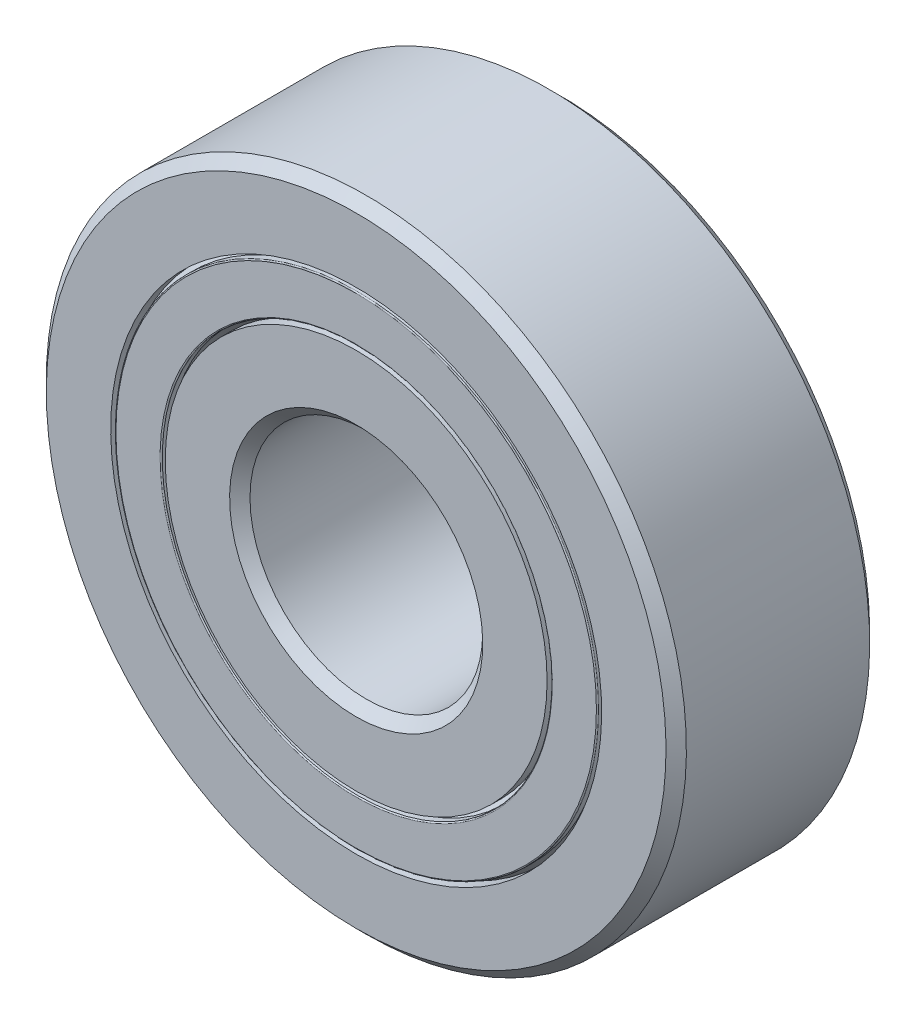
SolidWorks part; units mm, degrees
ref_plane "Front Plane" through (0, 0, 0) normal (0, 0, 1) x (1, 0, 0)
ref_plane "Top Plane" through (0, 0, 0) normal (0, 1, 0) x (1, 0, 0)
ref_plane "Right Plane" through (0, 0, 0) normal (1, 0, 0) x (0, 0, -1)
sketch "Sketch1" plane through (0, 0, 0) normal (0, 0, 1) x (1, 0, 0)
  line L0 (-11, 0) -> (11, 0) construction
  line L1 (-4, 0) -> (4, 0) construction
  circle A0 centre (0, 0) radius 4 construction
  circle A1 centre (0, 0) radius 11 construction
  point P3 (0, 0)
  point P6 (0, 0)
  point P7 (0, -4)
  point P11 (0, -11)
  point P12 (0, 4)
  point P13 (0, 11)
  dimension "OD" = 22
  dimension "ID" = 8
sketch "Sketch2" plane through (0, 0, 0) normal (1, 0, 0) x (0, 0, -1)
  line L0 (-3.5, 11) -> (3.5, 11) construction
  line L1 (0, 11) -> (0, -11) construction
  line L2 (3.15, 11) -> (-3.15, 11)
  line L3 (-3.15, 11) -> (-3.5, 10.65)
  line L4 (-3.5, 10.65) -> (-3.5, 8.4375)
  line L5 (-3.5, 8.4375) -> (-1.5556, 8.4375)
  line L6 (3.5, 8.4375) -> (1.5556, 8.4375)
  line L7 (3.5, 10.65) -> (3.5, 8.4375)
  line L8 (3.15, 11) -> (3.5, 10.65)
  line L9 (0, 11) -> (0, 7.5) construction
  line L10 (0, 7.5) -> (0, 4) construction
  line L11 (0, 11) -> (0, -11) construction
  line L12 (-3.5, 0) -> (3.5, 0) construction
  line L13 (3.5, 4) -> (-3.5, 4) construction
  line L14 (0, 9.3162) -> (0, 5.6838) construction
  line L15 (-3.5, -4) -> (3.5, -4) construction
  line L16 (-3.5, 4) -> (-3.5, -4) construction
  line L17 (3.5, 11) -> (3.5, -11) construction
  line L18 (-3.5, 8.4375) -> (-3.5, 8.3438) construction
  line L19 (-3.5, 8.3438) -> (-3.5, 8.25) construction
  line L20 (-3.5, 8.25) -> (-3.5, 8.1562) construction
  line L21 (-3.5, 8.1562) -> (-3.5, 8.0625) construction
  line L22 (-3.5, 8.0625) -> (-3.5, 7.9688) construction
  line L24 (-2.5278, 8.4375) -> (-2.5278, 7.5) construction
  arc A0 (-1.5556, 8.4375) -> (1.5556, 8.4375) centre (0, 7.5) cw
  circle A1 centre (0, 7.5) radius 1.8162 construction
  point P14 (0, 4)
  point P17 (0, 0)
  point P21 (0, 11)
  point P29 (0, 4)
  point P30 (0, -4)
  point P46 (-2.5278, 7.9688)
  dimension "Width" = 7
  dimension "D1" = 45
  dimension "D2" = 0.35
  dimension "D3" = 3.1111
  dimension "D4" = 0.9375
  dimension "For Shaft Diameter" = 8
  dimension "For Housing ID" = 22
sketch "Sketch3" plane through (0, 0, 0) normal (1, 0, 0) x (0, 0, -1)
  line L0 (3.15, 11) -> (3.5, 10.65) construction
  line L1 (3.5, 10.65) -> (3.5, 8.4375) construction
  line L2 (3.5, 8.4375) -> (1.5556, 8.4375) construction
  line L3 (-3.5, 8.4375) -> (-1.5556, 8.4375) construction
  line L4 (-3.5, 10.65) -> (-3.5, 8.4375) construction
  line L5 (-3.15, 11) -> (-3.5, 10.65) construction
  line L6 (3.15, 11) -> (-3.15, 11) construction
  line L7 (3.15, 11) -> (3.5, 10.65)
  line L8 (3.5, 10.65) -> (3.5, 8.4375)
  line L9 (3.5, 8.4375) -> (1.5556, 8.4375)
  line L10 (-3.5, 8.4375) -> (-1.5556, 8.4375)
  line L11 (-3.5, 10.65) -> (-3.5, 8.4375)
  line L12 (-3.15, 11) -> (-3.5, 10.65)
  line L13 (3.15, 11) -> (-3.15, 11)
  arc A0 (1.5556, 8.4375) -> (-1.5556, 8.4375) centre (0, 7.5) ccw construction
  arc A1 (1.5556, 8.4375) -> (-1.5556, 8.4375) centre (0, 7.5) ccw
revolve "Revolve1" add sketch "Sketch3" angle 360 about L12
sketch "Sketch4" plane through (0, 0, 0) normal (1, 0, 0) x (0, 0, -1)
  line L0 (0, 11) -> (0, -11) construction
  line L1 (0, 11) -> (0, -11) construction
  line L2 (-3.15, 4) -> (-3.5, 4.35)
  line L3 (-3.5, 4.35) -> (-3.5, 6.5625)
  line L5 (-3.5, 6.5625) -> (-1.5556, 6.5625)
  line L6 (-3.15, 4) -> (3.15, 4)
  line L8 (3.15, 4) -> (3.5, 4.35)
  line L10 (3.5, 4.35) -> (3.5, 6.5625)
  line L11 (3.5, 6.5625) -> (1.5556, 6.5625)
  line L12 (-3.5, 10.65) -> (-3.5, 8.4375) construction
  line L13 (3.15, 11) -> (3.5, 10.65) construction
  line L15 (3.5, -10.65) -> (3.5, 10.65) construction
  line L16 (3.15, 11) -> (3.15, -11) construction
  arc A1 (1.5556, 6.5625) -> (-1.5556, 6.5625) centre (0, 7.5) cw
  circle A2 centre (0, 7.5) radius 1.8162 construction
  point P1 (0, 4)
revolve "Revolve2" add sketch "Sketch4" angle 360 about L12
sketch "Sketch5" plane through (0, 0, 0) normal (1, 0, 0) x (0, 0, -1)
  line L0 (-1.8162, 7.5) -> (1.8162, 7.5)
  arc A2 (-1.8162, 7.5) -> (1.8162, 7.5) centre (0, 7.5) cw
  arc A3 (1.5556, 8.4375) -> (-1.5556, 8.4375) centre (0, 7.5) ccw construction
revolve "Revolve3" add sketch "Sketch5" angle 360 about L0
sketch "Sketch6" plane through (0, 0, 0) normal (1, 0, 0) x (0, 0, -1)
  line L0 (-3.5, 8.4375) -> (-3.5, 7.9688) construction
  line L1 (-3.5, 10.65) -> (-3.5, -10.65) construction
  line L2 (-3.5, 7.9688) -> (-3.5, 7.5) construction
  line L3 (-3.5, 7.5) -> (-3.5, 7.0312) construction
  line L4 (-3.5, 7.0312) -> (-3.5, 6.5625) construction
  line L5 (-3.5, 7.9688) -> (-3.2091, 7.9688) construction
  line L7 (-1.7547, 7.9687) -> (-1.7547, 7.0313) construction
  line L8 (-3.2091, 7.9688) -> (-2.9182, 7.9688) construction
  line L10 (0, 11) -> (0, -11) construction
  line L11 (0, 11) -> (0, -11) construction
  line L12 (-2.9182, 7.9688) -> (-2.6273, 7.9688) construction
  line L13 (-2.6273, 7.9688) -> (-2.3365, 7.9688) construction
  line L14 (-2.3365, 7.9688) -> (-2.0456, 7.9688) construction
  line L15 (-2.0456, 7.9688) -> (-1.7547, 7.9687) construction
  line L16 (-1.7547, 7.9687) -> (-2.0456, 7.9688)
  line L17 (-2.0456, 7.0313) -> (-2.3365, 7.0313) construction
  line L18 (-2.0456, 7.0313) -> (-1.7547, 7.0313)
  line L19 (-2.3365, 7.0313) -> (-2.3365, 7.9688) construction
  line L20 (-2.191, 7.9688) -> (-2.191, 7.0313) construction
  circle A0 centre (0, 7.5) radius 1.8162 construction
  circle A1 centre (0, 7.5) radius 1.8162 construction
  arc A2 (-2.0456, 7.9688) -> (-2.0456, 7.0313) centre (-1.3629, 7.5) ccw
  arc A3 (-1.7547, 7.9687) -> (-1.7547, 7.0313) centre (0, 7.5) ccw
  point P28 (-2.191, 7.5)
revolve "Revolve4" add sketch "Sketch6" angle 360 about L11
pattern_circular "CirPattern1" count 7 over 360 about axis through (0, 0, 3.5) along (0, 0, -1) of bodies 134 104
sketch "Sketch7" plane through (0, 0, 0) normal (0, 0, 1) x (1, 0, 0)
  line L0 (0, 6.5625) -> (0, 6.875) construction
  line L1 (0, 5.6838) -> (0, 9.3162) construction
  line L2 (0, 6.875) -> (0, 7.1875) construction
  line L3 (0, 7.1875) -> (0, 7.5) construction
  line L4 (0, 7.5) -> (0, 7.8125) construction
  line L5 (0, 7.8125) -> (0, 8.125) construction
  line L6 (0, 8.125) -> (0, 8.4375) construction
  line L7 (0, 10.65) -> (0, 8.4375) construction
  line L8 (0, 11) -> (0, -11) construction
  circle A0 centre (0, 0) radius 6.5625 construction
  circle A1 centre (0, 0) radius 7.5
  circle A2 centre (0, 0) radius 7.9688
  point P19 (0, 7.9688)
extrude "Boss-Extrude1" add sketch "Sketch7" along normal mid plane 1.1667 separate body
sketch "Sketch8" plane through (0, 0, 0) normal (1, 0, 0) x (0, 0, -1)
  line L0 (-3.5, 8.3438) -> (-3.5, 8.25) construction
  line L1 (-3.5, 8.2969) -> (-3.2407, 8.2969)
  line L2 (-3.5, 8.2969) -> (-3.5, 6.7031)
  line L3 (-3.5, 6.7031) -> (-3.2407, 6.7031)
  line L4 (-3.1111, 8.2969) -> (-3.1111, 6.7031)
  line L5 (0, 11) -> (0, 7.5) construction
  line L10 (-3.2407, 8.2969) -> (-3.1111, 8.4375)
  line L11 (-3.5, 8.4375) -> (-1.5556, 8.4375) construction
  line L12 (-3.1111, 8.4375) -> (-3.1111, 8.2969)
  line L13 (-3.2407, 6.7031) -> (-3.1111, 6.5625)
  line L14 (-3.1111, 6.5625) -> (-3.1111, 6.7031)
  line L15 (-3.5, 8.4375) -> (-3.3704, 8.4375) construction
  line L16 (3.5, 8.2969) -> (3.5, 6.7031)
  line L17 (3.5, 6.7031) -> (3.2407, 6.7031)
  line L18 (3.2407, 6.7031) -> (3.1111, 6.5625)
  line L19 (3.1111, 6.5625) -> (3.1111, 6.7031)
  line L20 (3.1111, 8.2969) -> (3.1111, 6.7031)
  line L21 (3.1111, 8.4375) -> (3.1111, 8.2969)
  line L22 (3.2407, 8.2969) -> (3.1111, 8.4375)
  line L23 (3.5, 8.2969) -> (3.2407, 8.2969)
  line L24 (-3.3704, 8.4375) -> (-3.2407, 8.4375) construction
  line L25 (-3.2407, 8.4375) -> (-3.1111, 8.4375) construction
  line L27 (-3.5, 6.5625) -> (-1.5556, 6.5625) construction
  point P23 (-3.5, 8.2969)
  dimension "D1" = 0.3889
revolve "Revolve5" add sketch "Sketch8" angle 360 about L12
fillet "Fillet1" radius 0.0389 2 edges at (0, -8.2969, 3.5) (0, -6.7031, 3.5)
fillet "Fillet2" radius 0.0389 2 edges at (0, -6.7031, -3.5) (0, -8.2969, -3.5)
equation "\"D2@Sketch2\" = \"Width@Sketch2\" * .05"
equation "\"D3@Sketch2\" = \"Width@Sketch2\" / 2.25"
equation "\"D4@Sketch2\"=( \"OD@Sketch1\" - \"Width@Sketch2\" )  *.5*.125"
equation "\"D1@Boss-Extrude1\" = \"Width@Sketch2\" / 6"
equation "\"D1@Sketch8\"=(\"Width@Sketch2\"-\"D3@Sketch2\")*.5*.2"
equation "\"D1@Fillet1\"=\"d1@sketch8\"*.1"
equation "\"D1@Fillet2\"=\"d1@fillet1\""
